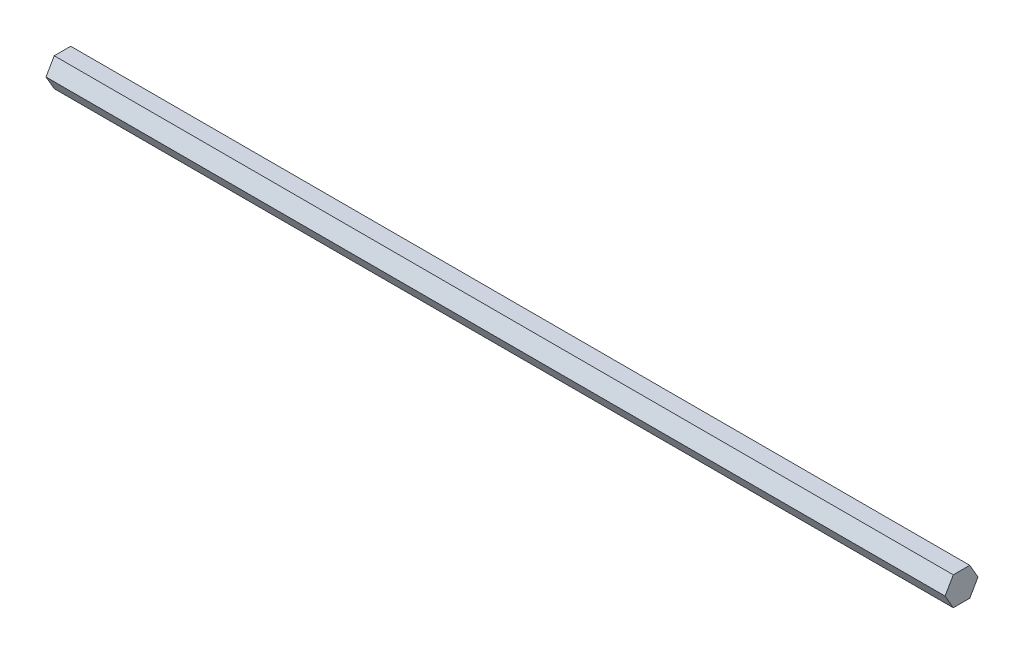
SolidWorks part; units mm, degrees
material "7075-T6 (SN)"
ref_plane "Front Plane" through (0, 0, 0) normal (0, 0, 1) x (1, 0, 0)
ref_plane "Top Plane" through (0, 0, 0) normal (0, 1, 0) x (1, 0, 0)
ref_plane "Right Plane" through (0, 0, 0) normal (1, 0, 0) x (0, 0, -1)
sketch "Sketch1" plane through (0, 0, 0) normal (1, 0, 0) x (0, 0, -1)
  line L1 (7.3323, 0) -> (3.6662, 6.35)
  line L2 (3.6662, 6.35) -> (-3.6662, 6.35)
  line L3 (-3.6662, 6.35) -> (-7.3323, 0)
  line L4 (-7.3323, 0) -> (-3.6662, -6.35)
  line L5 (-3.6662, -6.35) -> (3.6662, -6.35)
  line L6 (3.6662, -6.35) -> (7.3323, 0)
  circle A0 centre (0, 0) radius 6.35 construction
  dimension "D1" = 12.7
extrude "Boss-Extrude1" add sketch "Sketch1" along normal mid plane 400.05
ref_axis "Axis1" through (-230.505, 0, 0) along (1, 0, 0)
